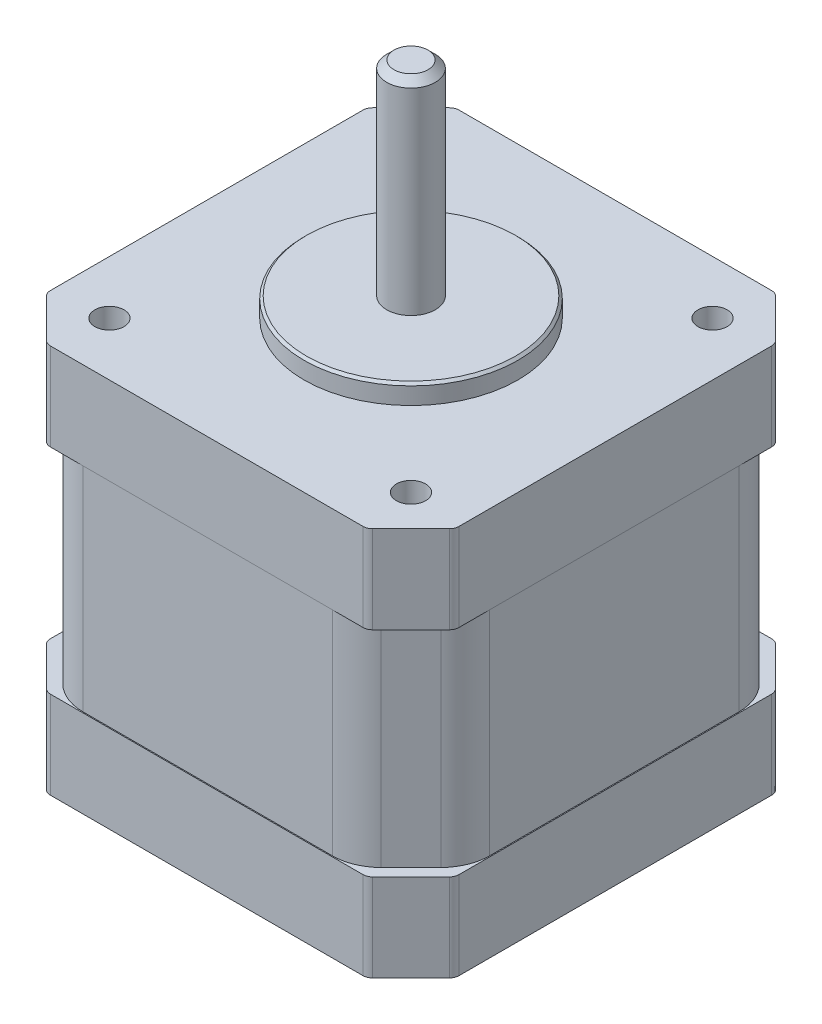
SolidWorks part; units mm, degrees
material "Chrome Stainless Steel"
ref_plane "Front Plane" through (0, 0, 0) normal (0, 0, 1) x (1, 0, 0)
ref_plane "Top Plane" through (0, 0, 0) normal (0, 1, 0) x (1, 0, 0)
ref_plane "Right Plane" through (0, 0, 0) normal (1, 0, 0) x (0, 0, -1)
sketch "Sketch1" plane through (0, 0, 0) normal (0, 1, 0) x (1, 0, 0)
  line L0 (-16.4767, 21) -> (-21, 16.4767)
  line L1 (16.4767, -21) -> (-16.4767, -21)
  line L2 (21, -16.4767) -> (21, 16.4767)
  line L3 (16.4767, 21) -> (-16.4767, 21)
  line L4 (-21, -16.4767) -> (-21, 16.4767)
  line L5 (21, -21) -> (-21, 21) construction
  line L6 (21, 21) -> (-21, -21) construction
  line L7 (21, 16.4767) -> (16.4767, 21)
  line L8 (21, -16.4767) -> (16.4767, -21)
  line L9 (-16.4767, -21) -> (-21, -16.4767)
  point P0 (0, 0)
  dimension "D1" = 42
  dimension "D2" = 42
  dimension "D3" = 53
extrude "Boss-Extrude1" add sketch "Sketch1" along normal blind 9
sketch "Sketch2" plane through (0, 9, 0) normal (0, 1, 0) x (1, 0, 0)
  line L1 (14.9, -20.9) -> (-14.9, -20.9)
  line L2 (20.9, -14.9) -> (20.9, 14.9)
  line L3 (14.9, 20.9) -> (-14.9, 20.9)
  line L4 (-20.9, -14.9) -> (-20.9, 14.9)
  line L5 (20.9, -20.9) -> (-20.9, 20.9) construction
  line L6 (20.9, 20.9) -> (-20.9, -20.9) construction
  line L8 (-14.9, 20.9) -> (-20.9, 14.9)
  line L9 (20.9, 14.9) -> (14.9, 20.9)
  line L10 (20.9, -14.9) -> (14.9, -20.9)
  line L11 (-14.9, -20.9) -> (-20.9, -14.9)
  line L15 (-21, 16.4767) -> (-21, -16.4767) construction
  line L16 (-16.4767, -21) -> (16.4767, -21) construction
  point P0 (0, 0)
  dimension "D2" = 0.1
  dimension "D3" = 0.1
extrude "Boss-Extrude4" add sketch "Sketch2" along normal blind 22
sketch "Sketch4" plane through (0, 31, 0) normal (0, 1, 0) x (1, 0, 0)
  line L0 (16.4767, 21) -> (-16.4767, 21) construction
  line L1 (16.4767, -21) -> (-16.4767, -21)
  line L2 (21, -16.4767) -> (21, 16.4767)
  line L3 (16.4767, 21) -> (-16.4767, 21)
  line L4 (-21, -16.4767) -> (-21, 16.4767)
  line L5 (21, -21) -> (-21, 21) construction
  line L6 (21, 21) -> (-21, -21) construction
  line L7 (-21, 16.4767) -> (-21, -16.4767) construction
  line L8 (-16.4767, 21) -> (-21, 16.4767)
  line L9 (21, 16.4767) -> (16.4767, 21)
  line L10 (21, -16.4767) -> (16.4767, -21)
  line L11 (-16.4767, -21) -> (-21, -16.4767)
  line L12 (-16.4767, 21) -> (-21, 16.4767) construction
  line L13 (-21, -16.4767) -> (-16.4767, -21) construction
  line L14 (16.4767, -21) -> (21, -16.4767) construction
  line L15 (21, 16.4767) -> (16.4767, 21) construction
  point P0 (0, 0)
extrude "Boss-Extrude5" add sketch "Sketch4" along normal blind 9
sketch "Sketch5" plane through (0, 40, 0) normal (0, 1, 0) x (1, 0, 0)
  circle A0 centre (0, 0) radius 11
  dimension "D1" = 22
extrude "Boss-Extrude6" add sketch "Sketch5" along normal blind 2
chamfer "Chamfer1" distance 0.25 angle 45 1 edges at (0, 42, 11)
sketch "Sketch6" plane through (0, 42, 0) normal (0, 1, 0) x (1, 0, 0)
  circle A0 centre (0, 0) radius 2.5
  dimension "D1" = 5
extrude "Boss-Extrude7" add sketch "Sketch6" along normal blind 21
chamfer "Chamfer2" distance 0.75 angle 45 1 edges at (0, 63, 2.5)
fillet "Fillet2" radius 1 16 edges at (16.4767, 4.5, -21) (21, 4.5, -16.4767) (21, 4.5, 16.4767) (16.4767, 4.5, 21) (-16.4767, 4.5, 21) (-21, 4.5, 16.4767) (-16.4767, 4.5, -21) (-21, 4.5, -16.4767) (-16.4767, 35.5, -21) (-21, 35.5, -16.4767) (16.4767, 35.5, -21) (21, 35.5, -16.4767) (21, 35.5, 16.4767) (16.4767, 35.5, 21) (-16.4767, 35.5, 21) (-21, 35.5, 16.4767)
fillet "Fillet3" radius 5 8 edges at (-14.9, 20, 20.9) (-20.9, 20, 14.9) (-20.9, 20, -14.9) (-14.9, 20, -20.9) (14.9, 20, -20.9) (20.9, 20, -14.9) (20.9, 20, 14.9) (14.9, 20, 20.9)
sketch "Sketch7" plane through (0, 0, 0) normal (0, -1, 0) x (1, 0, 0)
  circle A0 centre (0, 0) radius 4.5
  dimension "D1" = 9
extrude "Cut-Extrude1" cut sketch "Sketch7" against normal blind 3
sketch "Sketch8" plane through (0, 40, 0) normal (0, 1, 0) x (1, 0, 0)
  line L1 (15.5, 15.5) -> (-15.5, 15.5) construction
  line L2 (15.5, 15.5) -> (15.5, -15.5) construction
  line L3 (15.5, -15.5) -> (-15.5, -15.5) construction
  line L4 (-15.5, 15.5) -> (-15.5, -15.5) construction
  line L5 (15.5, 15.5) -> (-15.5, -15.5) construction
  line L6 (15.5, -15.5) -> (-15.5, 15.5) construction
  circle A0 centre (-15.5, -15.5) radius 1.5
  circle A1 centre (-15.5, 15.5) radius 1.5
  circle A2 centre (15.5, 15.5) radius 1.5
  circle A3 centre (15.5, -15.5) radius 1.5
  point P0 (0, 0)
  dimension "D3" = 3
  dimension "D4" = 3
  dimension "D5" = 3
  dimension "D6" = 3
  dimension "D1" = 31
  dimension "D2" = 31
extrude "Cut-Extrude2" cut sketch "Sketch8" against normal through all
sketch "Sketch9" plane through (0, 0, 0) normal (0, -1, 0) x (1, 0, 0)
  circle A0 centre (-15.5, 15.5) radius 3
  circle A1 centre (15.5, 15.5) radius 3
  circle A2 centre (-15.5, -15.5) radius 3
  circle A3 centre (15.5, -15.5) radius 3
  dimension "D1" = 6
  dimension "D2" = 6
  dimension "D3" = 6
  dimension "D4" = 6
extrude "Cut-Extrude3" cut sketch "Sketch9" against normal blind 1.3
